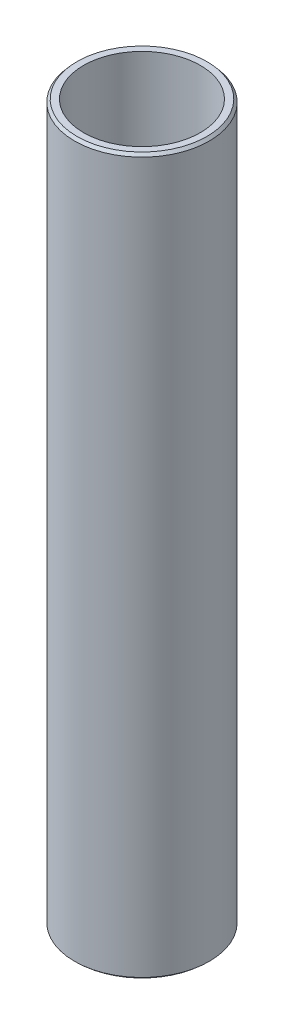
SolidWorks part; units mm, degrees
ref_plane "Front Plane" through (0, 0, 0) normal (0, 0, 1) x (1, 0, 0)
ref_plane "Top Plane" through (0, 0, 0) normal (0, 1, 0) x (1, 0, 0)
ref_plane "Right Plane" through (0, 0, 0) normal (1, 0, 0) x (0, 0, -1)
sketch "Sketch1" plane through (0, 0, 0) normal (0, 1, 0) x (1, 0, 0)
  circle A0 centre (0, 0) radius 55
  dimension "SHAFT_OD" = 110
extrude "Boss-Extrude1" add sketch "Sketch1" along normal blind 584.3673
sketch "Sketch2" plane through (0, 0, 0) normal (0, 1, 0) x (1, 0, 0)
  circle A0 centre (0, 0) radius 47.6697
  dimension "BORE_D" = 95.3395
extrude "Cut-Extrude1" cut sketch "Sketch2" along normal through all
chamfer "Chamfer1" distance 2.24 angle 41.292 2 edges at (0, 584.3673, 55) (0, 0, 55) first distance on face at (0, 584.3673, 55) first distance on face at (0, 0, 47.6697)
